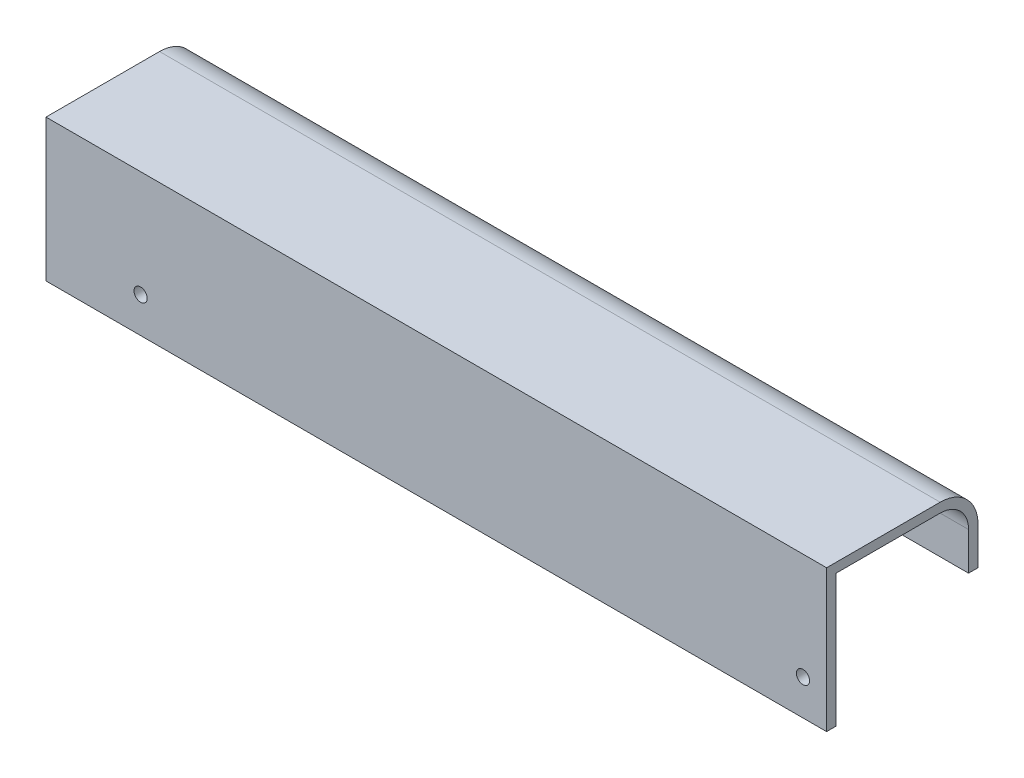
SolidWorks part; units mm, degrees
ref_plane "Front Plane" through (0, 0, 0) normal (0, 0, 1) x (1, 0, 0)
ref_plane "Top Plane" through (0, 0, 0) normal (0, 1, 0) x (1, 0, 0)
ref_plane "Right Plane" through (0, 0, 0) normal (1, 0, 0) x (0, 0, -1)
sketch "Sketch1" plane through (0, 0, 0) normal (0, 1, 0) x (1, 0, 0)
  line L0 (53.34, 0) -> (-66.8241, 0) construction
  line L1 (-190.5, 0) -> (19.05, 0)
  line L2 (-190.5, 0) -> (-190.5, 38.1)
  line L3 (-190.5, 38.1) -> (19.05, 38.1)
  line L4 (19.05, 0) -> (19.05, 38.1)
  line L5 (-190.5, 38.1) -> (-190.5, 0) construction
  dimension "D1" = 209.55
extrude "Boss-Extrude1" add sketch "Sketch1" along normal blind 20.32
fillet "Fillet1" radius 10.16 1 edges at (-85.725, 20.32, -38.1)
sketch "Sketch2" plane through (0, 0, 0) normal (0, 0, 1) x (1, 0, 0)
  line L0 (19.05, 20.32) -> (19.05, 0) construction
  line L1 (-190.5, 20.32) -> (19.05, 20.32)
  line L2 (-190.5, 20.32) -> (-190.5, -17.78)
  line L3 (-190.5, -17.78) -> (19.05, -17.78)
  line L4 (19.05, 20.32) -> (19.05, -17.78)
  circle A0 centre (-165.1, -8.255) radius 1.778
  circle A1 centre (12.7, -8.255) radius 1.778
  circle A2 centre (12.7, -8.255) radius 1.778 construction
  circle A3 centre (-165.1, -8.255) radius 1.778 construction
extrude "Boss-Extrude2" add sketch "Sketch2" along normal blind 2.54
shell "Shell5" thickness 2.54 removed face at (-190.5, 2.4777, -14.452)
sketch "Sketch3" plane through (-190.5, 0, 0) normal (-1, 0, 0) x (0, 0, 1)
  line L0 (-35.56, 2.54) -> (0, 2.54) construction
  line L1 (0, 0) -> (-35.56, 0)
  line L2 (0, 0) -> (0, 17.78)
  line L4 (-35.56, 0) -> (-35.56, 2.54)
  line L5 (0, 2.54) -> (-35.56, 2.54) construction
  line L6 (0, 17.78) -> (0, 2.54) construction
  line L7 (0, 17.78) -> (-27.94, 17.78)
  line L9 (-35.56, 10.16) -> (-35.56, 2.54)
  arc A0 (-27.94, 17.78) -> (-35.56, 10.16) centre (-27.94, 10.16) ccw
extrude "Cut-Extrude1" cut sketch "Sketch3" against normal up to surface (209.55 mm away) up to face at (19.05, 2.4777, -14.452)
sketch "Sketch4" plane through (-190.5, 0, 0) normal (-1, 0, 0) x (0, 0, 1)
  line L0 (-35.56, 0) -> (-30.48, 0)
  line L1 (0, 0) -> (0, 17.78)
  line L2 (0, 17.78) -> (-27.94, 17.78)
  line L4 (-35.56, 10.16) -> (-35.56, 0)
  line L5 (-5.08, 0) -> (0, 0)
  line L6 (-35.56, 0) -> (0, 0) construction
  arc A0 (-27.94, 17.78) -> (-35.56, 10.16) centre (-27.94, 10.16) ccw
  arc A1 (-27.94, 17.78) -> (-35.56, 10.16) centre (-27.94, 10.16) ccw construction
  ellipse E0 centre (-17.78, 0) end of major axis (-30.48, 0) minor radius 12.7 (-5.08, 0) -> (-30.48, 0) ccw
  point P17 (-17.78, 0)
  dimension "D1" = 12.7
  dimension "D2" = 12.7
extrude "Boss-Extrude3" add sketch "Sketch4" against normal blind 50.8 separate body
